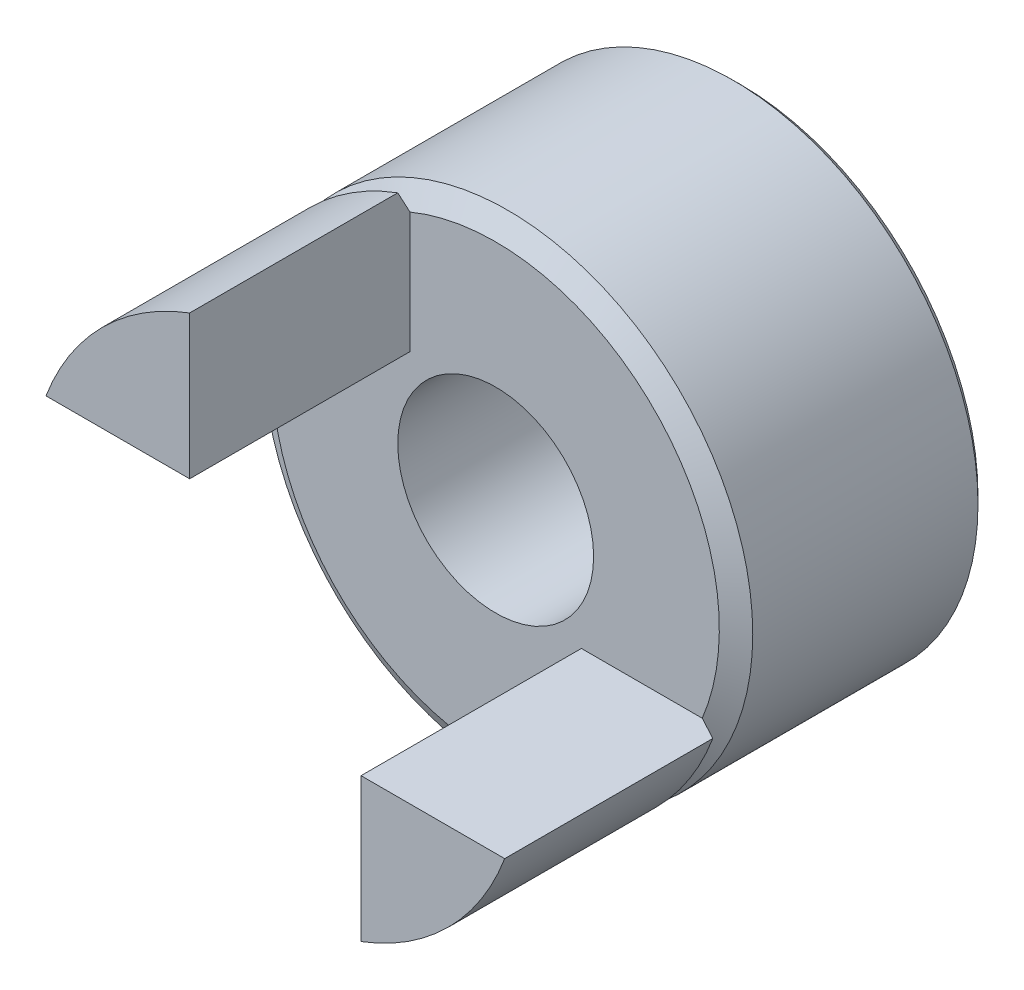
SolidWorks part; units mm, degrees
ref_plane "정면" through (0, 0, 0) normal (0, 0, 1) x (1, 0, 0)
ref_plane "윗면" through (0, 0, 0) normal (0, 1, 0) x (1, 0, 0)
ref_plane "우측면" through (0, 0, 0) normal (1, 0, 0) x (0, 0, -1)
sketch "스케치1" plane through (0, 0, 0) normal (0, 0, 1) x (1, 0, 0)
  circle A0 centre (0, 0) radius 10
  circle A1 centre (0, 0) radius 4
  dimension "D1" = 8
  dimension "D2" = 20
extrude "보스-돌출1" add sketch "스케치1" along normal blind 10
chamfer "모따기1" distance 0.3 angle 45 2 edges at (4, 0, 0) (10, 0, 0)
sketch "스케치2" plane through (0, 0, 10) normal (0, 0, 1) x (1, 0, 0)
  line L1 (-10, -3.5) -> (10, -3.5)
  line L2 (-10, -3.5) -> (-10, 3.5)
  line L3 (-10, 3.5) -> (10, 3.5)
  line L4 (10, -3.5) -> (10, 3.5)
  line L5 (-10, -3.5) -> (10, 3.5) construction
  line L6 (-10, 3.5) -> (10, -3.5) construction
  line L7 (-3.5, -10) -> (3.5, -10)
  line L8 (-3.5, -10) -> (-3.5, 10)
  line L9 (-3.5, 10) -> (3.5, 10)
  line L10 (3.5, -10) -> (3.5, 10)
  line L11 (-3.5, -10) -> (3.5, 10) construction
  line L12 (-3.5, 10) -> (3.5, -10) construction
  circle A1 centre (0, 0) radius 10
  circle A2 centre (0, 0) radius 10
  circle M5 centre (0, 0) radius 10
  dimension "D2" = 7
  dimension "D1" = 0
extrude "보스-돌출2" add sketch "스케치2" along normal blind 9 contours L3 L8 M5 | L10 L1 M5 region at (-5.735, 5.735, 10) region at (5.735, -5.735, 10)
sketch "스케치3" plane through (0, 0, 0) normal (0, 1, 0) x (1, 0, 0)
  line L1 (9.134, -10) -> (10, -10.5)
  line L2 (10, -10.5) -> (10, -9.5)
  line L3 (10, -9.5) -> (9.134, -10)
  line L7 (0, 0) -> (0, -17.4659) construction
  circle A0 centre (9.7113, -10) radius 0.2887 construction
  dimension "D1" = 10
  dimension "D2" = 1
  dimension "D3" = 9.5
revolve "컷-회전1" cut sketch "스케치3" angle 360 about L7
